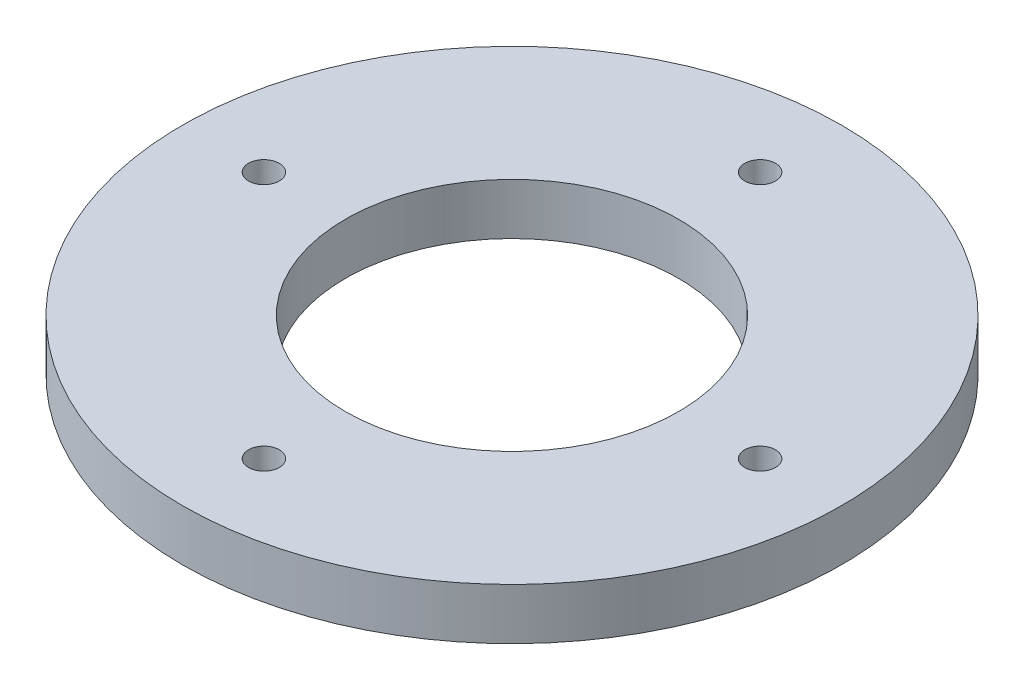
SolidWorks part; units mm, degrees
ref_plane "Front Plane" through (0, 0, 0) normal (0, 0, 1) x (1, 0, 0)
ref_plane "Top Plane" through (0, 0, 0) normal (0, 1, 0) x (1, 0, 0)
ref_plane "Right Plane" through (0, 0, 0) normal (1, 0, 0) x (0, 0, -1)
sketch "Sketch1" plane through (0, 0, 0) normal (0, 1, 0) x (1, 0, 0)
  circle A0 centre (0, 0) radius 32.135
  circle A1 centre (0, 0) radius 16.25
  dimension "D1" = 64.27
  dimension "D2" = 32.5
extrude "Boss-Extrude1" add sketch "Sketch1" along normal mid plane 5
sketch "Sketch2" plane through (0, 2.5, 0) normal (0, 1, 0) x (1, 0, 0)
  line L0 (0, 16.25) -> (0, 32.135) construction
  circle A0 centre (0, 24.1925) radius 1.5
  circle A1 centre (0, 0) radius 16.25 construction
  circle A2 centre (0, 0) radius 32.135 construction
  dimension "D1" = 3
extrude "Cut-Extrude1" cut sketch "Sketch2" against normal through all
pattern_circular "CirPattern1" count 4 over 360 about axis through (0, 2.5, 0) along (0, -1, 0) of "Cut-Extrude1" reverse direction yes
